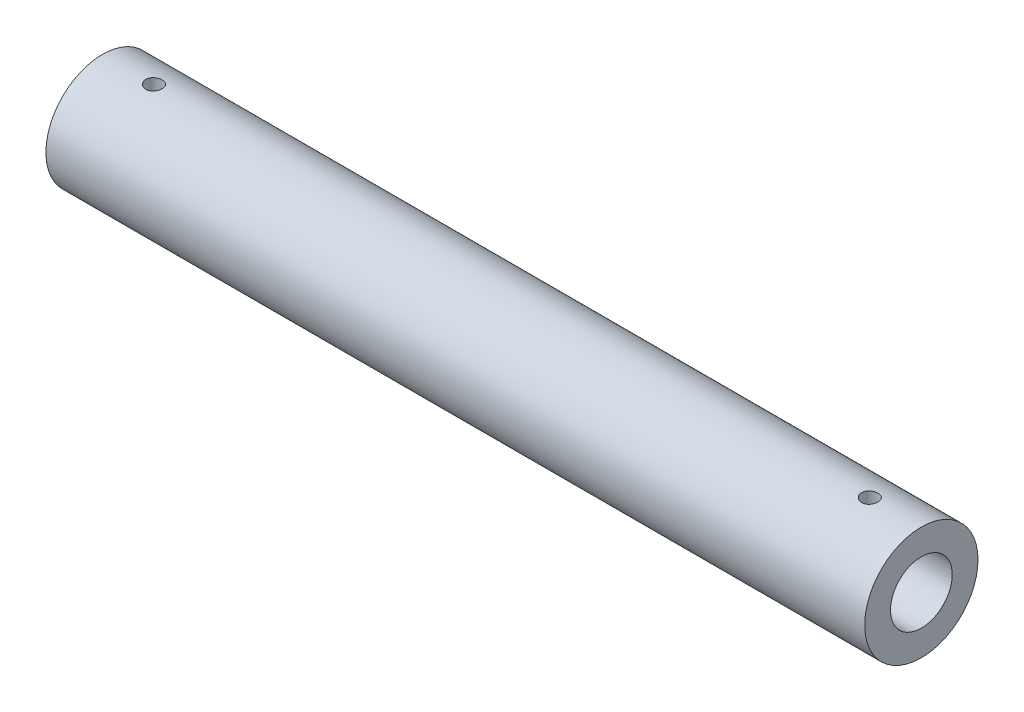
SolidWorks part; units mm, degrees
material "PVC Rigid"
ref_plane "Front Plane" through (0, 0, 0) normal (0, 0, 1) x (1, 0, 0)
ref_plane "Top Plane" through (0, 0, 0) normal (0, 1, 0) x (1, 0, 0)
ref_plane "Right Plane" through (0, 0, 0) normal (1, 0, 0) x (0, 0, -1)
sketch "Sketch2" plane through (0, 0, 0) normal (1, 0, 0) x (0, 0, -1)
  circle A0 centre (0, 0) radius 6
  circle A1 centre (0, 0) radius 11
  dimension "D1" = 5
  dimension "D2" = 12
extrude "Boss-Extrude1" add sketch "Sketch2" along normal blind 158.975
sketch "Sketch3" plane through (0, 0, 0) normal (0, 1, 0) x (1, 0, 0)
  line L0 (0, 0) -> (158.975, 0) construction
  line L1 (158.975, -11) -> (158.975, 11) construction
  circle A0 centre (10, 0) radius 1.5875
  circle A1 centre (148.975, 0) radius 1.5875
  dimension "D1" = 3.175
  dimension "D2" = 10
  dimension "D3" = 10
extrude "Cut-Extrude1" cut sketch "Sketch3" against normal through all and the other way through all
